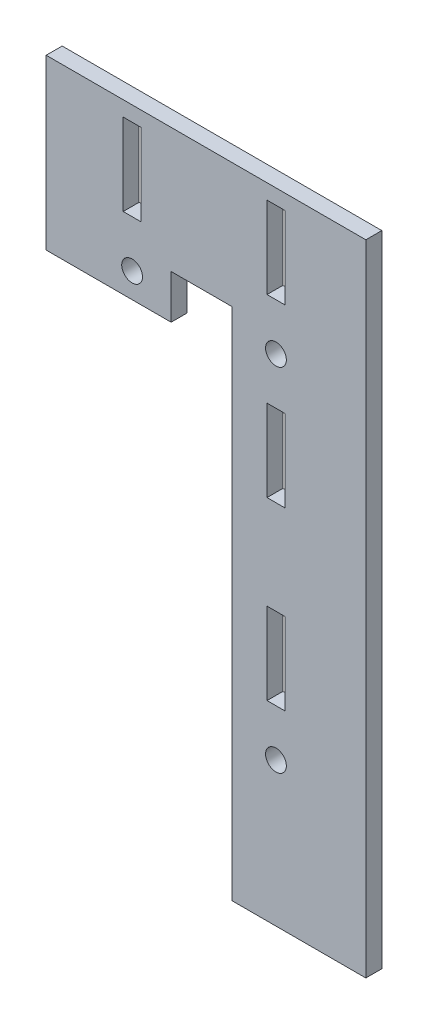
SolidWorks part; units mm, degrees
ref_plane "Front Plane" through (0, 0, 0) normal (1, 0, 0) x (0, 1, 0)
ref_plane "Top Plane" through (0, 0, 0) normal (0, 0, 1) x (0, 1, 0)
ref_plane "Right Plane" through (0, 0, 0) normal (0, 1, 0) x (-1, 0, 0)
sketch "Sketch1" plane through (0, 0, 0) normal (0, 0, 1) x (0, 1, 0)
  line L1 (-50.8, 25.4) -> (50.8, 25.4)
  line L2 (-50.8, 25.4) -> (-50.8, -25.4)
  line L3 (-50.8, -25.4) -> (50.8, -25.4)
  line L4 (50.8, 25.4) -> (50.8, -25.4)
  line L5 (-50.8, 25.4) -> (50.8, -25.4) construction
  line L6 (-50.8, -25.4) -> (50.8, 25.4) construction
  point P0 (0, 0)
  dimension "D1" = 101.6
  dimension "D2" = 50.8
extrude "Boss-Extrude1" add sketch "Sketch1" along normal blind 2.54
sketch "Sketch2" plane through (0, 0, 2.54) normal (0, 0, 1) x (1, 0, 0)
  line L0 (11.1159, -27.94) -> (11.1159, 27.94) construction
  line L1 (11.1159, 27.94) -> (-11.7441, 27.94) construction
  line L2 (-11.7441, 27.94) -> (-11.7441, -27.94) construction
  line L3 (-11.7441, -27.94) -> (11.1159, -27.94) construction
  line L4 (25.4, 50.8) -> (-25.4, 50.8) construction
  circle A0 centre (11.1159, 27.94) radius 1.651
  circle A1 centre (11.1159, -27.94) radius 1.651
  circle A2 centre (-11.7441, 27.94) radius 1.651
  dimension "D3" = 3.302
  dimension "D1" = 55.88
  dimension "D2" = 22.86
  dimension "D4" = 22.86
extrude "Cut-Extrude1" cut sketch "Sketch2" against normal through all
sketch "Sketch3" plane through (0, 0, 2.54) normal (0, 0, 1) x (1, 0, 0)
  line L1 (12.5358, -7.4701) -> (9.696, -7.4701)
  line L2 (12.5358, -7.4701) -> (12.5358, -20.4699)
  line L3 (12.5358, -20.4699) -> (9.696, -20.4699)
  line L4 (9.696, -7.4701) -> (9.696, -20.4699)
  line L5 (12.5358, -7.4701) -> (9.696, -20.4699) construction
  line L6 (12.5358, -20.4699) -> (9.696, -7.4701) construction
  line L7 (12.5358, 7.4701) -> (9.696, 7.4701)
  line L8 (12.5358, 7.4701) -> (12.5358, 20.4699)
  line L9 (12.5358, 20.4699) -> (9.696, 20.4699)
  line L10 (9.696, 7.4701) -> (9.696, 20.4699)
  line L11 (12.5358, 7.4701) -> (9.696, 20.4699) construction
  line L12 (12.5358, 20.4699) -> (9.696, 7.4701) construction
  line L13 (12.5358, 35.4101) -> (9.696, 35.4101)
  line L14 (12.5358, 35.4101) -> (12.5358, 48.4099)
  line L15 (12.5358, 48.4099) -> (9.696, 48.4099)
  line L16 (9.696, 35.4101) -> (9.696, 48.4099)
  line L17 (12.5358, 35.4101) -> (9.696, 48.4099) construction
  line L18 (12.5358, 48.4099) -> (9.696, 35.4101) construction
  line L19 (-10.3242, 35.4101) -> (-13.164, 35.4101)
  line L20 (-10.3242, 35.4101) -> (-10.3242, 48.4099)
  line L21 (-10.3242, 48.4099) -> (-13.164, 48.4099)
  line L22 (-13.164, 35.4101) -> (-13.164, 48.4099)
  line L23 (-10.3242, 35.4101) -> (-13.164, 48.4099) construction
  line L24 (-10.3242, 48.4099) -> (-13.164, 35.4101) construction
  circle A0 centre (11.1159, -27.94) radius 1.651 construction
  circle A3 centre (11.1159, 27.94) radius 1.651 construction
  point P0 (11.1159, -13.97)
  point P10 (11.1159, 13.97)
  point P14 (11.1159, 41.91)
  point P19 (-11.7441, 41.91)
  point P22 (13.5743, -25.7483)
  point P23 (0, 0)
  point P24 (0, 0)
  point P29 (0, 0)
  point P30 (0, 0)
  point P31 (0, 0)
  dimension "D1" = 7.4701
  dimension "D2" = 1.4199
  dimension "D8" = 1.4199
  dimension "D3" = 12.9997
  dimension "D4" = 27.94
  dimension "D5" = 27.94
  dimension "D6" = 22.86
  dimension "D7" = 2.8397
extrude "Cut-Extrude4" cut sketch "Sketch3" against normal through all
sketch "Sketch5" plane through (0, 0, 2.54) normal (0, 0, 1) x (1, 0, 0)
  line L0 (4.108, -50.8) -> (4.108, 30.9651)
  line L1 (-25.4, -50.8) -> (25.4, -50.8) construction
  line L2 (4.108, 30.9651) -> (-5.544, 30.9651)
  line L3 (-5.544, 30.9651) -> (-5.544, 23.9801)
  line L4 (-5.544, 23.9801) -> (-25.4, 23.9801)
  line L5 (-25.4, 50.8) -> (-25.4, -50.8) construction
  line L6 (-25.4, 23.9801) -> (-25.4, -50.8)
  line L7 (-25.4, -50.8) -> (4.108, -50.8)
  dimension "D1" = 5.588
  dimension "D2" = 4.445
  dimension "D3" = 11.43
  dimension "D4" = 15.24
extrude "Cut-Extrude5" cut sketch "Sketch5" against normal through all
